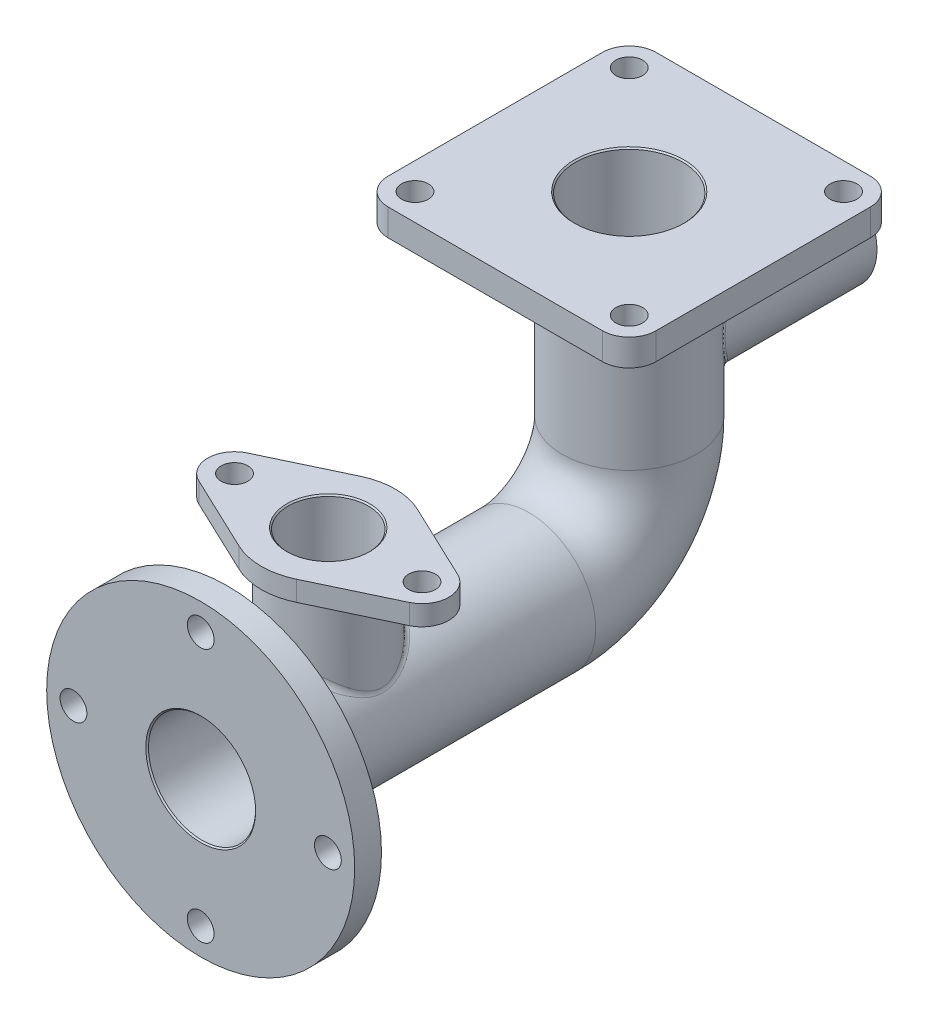
SolidWorks part; units mm, degrees
ref_plane "Front Plane" through (0, 0, 0) normal (0, 0, 1) x (1, 0, 0)
ref_plane "Top Plane" through (0, 0, 0) normal (0, 1, 0) x (1, 0, 0)
ref_plane "Right Plane" through (0, 0, 0) normal (1, 0, 0) x (0, 0, -1)
sketch "Sketch2" plane through (0, 0, 0) normal (0, 0, 1) x (1, 0, 0)
  circle A0 centre (0, 0) radius 40
  circle A1 centre (0, 0) radius 50
  dimension "D1" = 80
  dimension "D2" = 100
sketch "Sketch3" plane through (0, 0, 0) normal (1, 0, 0) x (0, 0, -1)
  line L0 (0, 0) -> (225, 0)
  line L1 (300, 75) -> (300, 200)
  line L2 (0, 50) -> (0, -50) construction
  arc A0 (225, 0) -> (300, 75) centre (225, 75) ccw
  dimension "D1" = 75
  dimension "D2" = 300
sweep "Sweep1" add profiles "Sketch2" path "Sketch3"
sketch "Sketch4" plane through (0, 0, 0) normal (0, 0, 1) x (1, 0, 0)
  circle A0 centre (0, 0) radius 40
  circle A2 centre (0, 0) radius 115
  circle A3 centre (95, 0) radius 10
  circle A4 centre (0, 95) radius 10
  circle A5 centre (0, -95) radius 10
  circle A6 centre (-95, 0) radius 10
  point P7 (0, 0)
  point P8 (0, 0)
  point P16 (0, 0)
  dimension "D1" = 95
  dimension "D2" = 230
  dimension "D3" = 20
  dimension "D5" = 80
  dimension "D4" = 4
extrude "Boss-Extrude1" add sketch "Sketch4" along normal blind 20
sketch "Sketch5" plane through (0, 200, 0) normal (0, 1, 0) x (1, 0, 0)
  line L0 (0, 300) -> (0, 200) construction
  line L1 (-80, 400) -> (80, 400)
  line L2 (-100, 380) -> (-100, 220)
  line L3 (-80, 200) -> (80, 200)
  line L4 (100, 380) -> (100, 220)
  line L5 (-100, 400) -> (100, 200) construction
  line L6 (-100, 200) -> (100, 400) construction
  circle A0 centre (0, 300) radius 40
  circle A1 centre (-80, 220) radius 10
  circle A2 centre (-80, 380) radius 10
  circle A3 centre (80, 380) radius 10
  circle A4 centre (80, 220) radius 10
  arc A5 (-100, 220) -> (-80, 200) centre (-80, 220) ccw
  arc A6 (80, 200) -> (100, 220) centre (80, 220) ccw
  arc A7 (80, 400) -> (100, 380) centre (80, 380) cw
  arc A8 (-80, 400) -> (-100, 380) centre (-80, 380) ccw
  dimension "D3" = 20
  dimension "D4" = 20
  dimension "D5" = 20
  dimension "D6" = 20
  dimension "D7" = 20
  dimension "D9" = 80
  dimension "D1" = 200
  dimension "D2" = 200
  dimension "D8" = 80
extrude "Boss-Extrude2" add sketch "Sketch5" along normal blind 20
sketch "Sketch6" plane through (0, 0, 0) normal (1, 0, 0) x (0, 0, -1)
  line L0 (0, 0) -> (199.9787, 0) construction
  line L2 (0, 100) -> (75, 100) construction
  line L3 (75, 100) -> (75, 0) construction
sketch "Sketch7" plane through (0, 0, 0) normal (0, 1, 0) x (1, 0, 0)
  line L0 (0, 0) -> (0, 199.9787) construction
  circle A1 centre (0, 75.2571) radius 40
  point P1 (0, 0)
  dimension "D2" = 80
ref_plane "Plane1" through (0, 115, 0) normal (0, 1, 0) x (1, 0, 0)
sketch "Sketch9" plane through (0, 115, 0) normal (0, 1, 0) x (1, 0, 0)
  circle A0 centre (0, 75.2571) radius 40
  circle A1 centre (0, 75.2571) radius 30
extrude "Boss-Extrude5" add sketch "Sketch9" against normal up to surface (65 mm away) up to face at (50, 0, -225)
sketch "Sketch10" plane through (0, 115, 0) normal (0, 1, 0) x (1, 0, 0)
  circle A0 centre (0, 75.2571) radius 30
extrude "Cut-Extrude7" cut sketch "Sketch10" against normal mid plane 181 contours A0
sketch "Sketch11" plane through (0, 115, 0) normal (0, 1, 0) x (1, 0, 0)
  line L0 (0, 75.2571) -> (-70, 75.2571) construction
  line L1 (0, 75.2571) -> (70, 75.2571) construction
  line L2 (-78.5714, 93.3273) -> (-21.4286, 120.4325)
  line L3 (-78.5714, 57.1869) -> (-21.4286, 30.0817)
  line L4 (21.4286, 120.4325) -> (78.5714, 93.3273)
  line L5 (21.4286, 30.0817) -> (78.5714, 57.1869)
  circle A0 centre (0, 75.2571) radius 30
  arc A1 (-21.4286, 30.0817) -> (21.4286, 30.0817) centre (0, 75.2571) ccw
  circle A2 centre (-70, 75.2571) radius 10
  circle A3 centre (70, 75.2571) radius 10
  arc A4 (-78.5714, 93.3273) -> (-78.5714, 57.1869) centre (-70, 75.2571) ccw
  arc A5 (78.5714, 57.1869) -> (78.5714, 93.3273) centre (70, 75.2571) ccw
  arc A6 (21.4286, 120.4325) -> (-21.4286, 120.4325) centre (0, 75.2571) ccw
  point P3 (0, 0)
  point P14 (-156.9953, 133.362)
  dimension "D1" = 20
  dimension "D2" = 40
  dimension "D3" = 10
  dimension "D4" = 20
  dimension "D5" = 30
  dimension "D6" = 50
  dimension "D7" = 140
  dimension "D8" = 70
extrude "Boss-Extrude6" add sketch "Sketch11" against normal blind 15
ref_plane "Plane2" through (0, 0, -445) normal (0, 0, 1) x (1, 0, 0)
sketch "Sketch12" plane through (0, 0, -445) normal (0, 0, 1) x (1, 0, 0)
  line L0 (0, 0) -> (0, 130) construction
  line L1 (40, 0) -> (-40, 0) construction
  circle A0 centre (0, 130) radius 30
  circle A1 centre (0, 130) radius 40
  dimension "D1" = 30
  dimension "D2" = 40
extrude "Boss-Extrude7" add sketch "Sketch12" along normal up to surface (105 mm away) up to face at (50, 200, -300)
sketch "Sketch14" plane through (0, 0, -445) normal (0, 0, 1) x (1, 0, 0)
  circle A2 centre (0, 130) radius 30
extrude "Cut-Extrude8" cut sketch "Sketch14" along normal mid plane 284 contours A2
fillet "Fillet1" radius 5 1 edges at (-4.6858, 49.7799, -114.9817)
fillet "Fillet2" radius 5 1 edges at (50, 0, 0)
fillet "Fillet3" radius 5 2 edges at (50, 200, -300) (39.3831, 123.0021, -330.8054)
chamfer "Chamfer1" distance 1 angle 45 3 edges at (0, 115, -45.2571) (40, 0, 20) (0, 220, -260)
fillet "Fillet4" radius 1 1 edges at (30, 130, -445)
